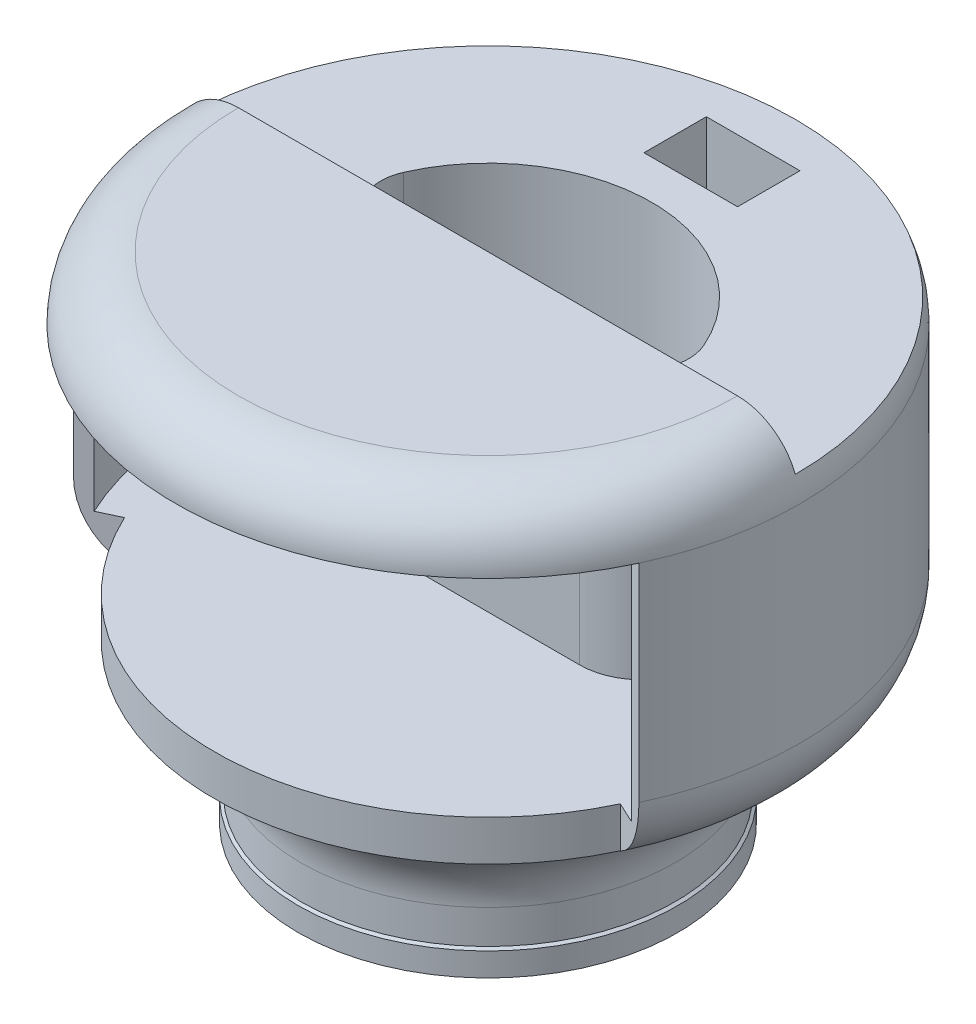
SolidWorks part; units mm, degrees
ref_plane "Front Plane" through (0, 0, 0) normal (0, 0, 1) x (1, 0, 0)
ref_plane "Top Plane" through (0, 0, 0) normal (0, 1, 0) x (1, 0, 0)
ref_plane "Right Plane" through (0, 0, 0) normal (1, 0, 0) x (0, 0, -1)
sketch "Sketch1" plane through (0, 0, 0) normal (0, 0, 1) x (1, 0, 0)
  line L0 (0, 0) -> (0, 90.2242) construction
  line L28 (0, 63.4279) -> (32, 63.4279)
  line L29 (40, 55.4279) -> (40, 28.8468)
  line L30 (22.5, 0) -> (24.35, 0)
  line L31 (24.35, 0) -> (24.35, 3)
  line L32 (24.35, 3) -> (24, 3.25)
  line L33 (24, 3.25) -> (24, 7.5811)
  line L34 (28.5399, 15.9588) -> (35.4601, 20.4691)
  line L35 (0, 13) -> (22, 13)
  line L36 (22.5, 12.5) -> (22.5, 0)
  line L37 (0, 13) -> (0, 63.4279)
  arc A0 (22, 13) -> (22.5, 12.5) centre (22, 12.5) cw
  arc A1 (24, 7.5811) -> (28.5399, 15.9588) centre (34, 7.5811) cw
  arc A2 (35.4601, 20.4691) -> (40, 28.8468) centre (30, 28.8468) ccw
  arc A3 (32, 63.4279) -> (40, 55.4279) centre (32, 55.4279) cw
  point P11 (22.9, 63.4279)
  point P18 (22.5, 13)
  point P21 (24, 13)
  point P24 (40, 23.4279)
  point P27 (40, 63.4279)
  point P28 (28.5604, 23.4279)
  point P31 (22.5, 17)
  dimension "D8" = 9.75
  dimension "D9" = 0.5
  dimension "D4" = 1.85
  dimension "D1" = 22.5
  dimension "D10" = 10
  dimension "D11" = 10
  dimension "D12" = 8
  dimension "D2" = 40
  dimension "D3" = 40
  dimension "D5" = 1.5
  dimension "D6" = 3
  dimension "D7" = 13
revolve "Revolve1" add sketch "Sketch1" angle 360 about L0
ref_plane "Plane1" through (0, 13, 0) normal (0, -1, 0) x (-1, 0, 0)
sketch "Sketch18" plane through (0, 0, 0) normal (0, 0, 1) x (1, 0, 0)
  line L0 (0, 0) -> (0, 101.5813) construction
  line L1 (-24.35, 0) -> (24.35, 0) construction
sketch "Sketch3" plane through (0, 0, 0) normal (0, 0, 1) x (1, 0, 0)
  point P0 (1.2404, 19.1989)
ref_point "Point1"
ref_plane "Plane2" through (0, 0, 22.9) normal (0, 0, 1) x (1, 0, 0)
ref_plane "Plane3" through (0, 0, 40) normal (0, 0, 1) x (1, 0, 0)
ref_plane "Plane4" through (0, 55.4279, 0) normal (0, 1, 0) x (1, 0, 0)
sketch "Sketch9" plane through (0, 55.4279, 0) normal (0, 1, 0) x (1, 0, 0)
  circle A7 centre (0, 0) radius 38
  circle A8 centre (0, 0) radius 40 construction
  circle A9 centre (0, 0) radius 23
  dimension "D1" = 2
  dimension "D2" = 46
ref_plane "Plane5" through (0, 13, 0) normal (0, -1, 0) x (-1, 0, 0)
sketch "Sketch11" plane through (0, 13, 0) normal (0, -1, 0) x (-1, 0, 0)
  line L0 (-21, 0) -> (21, 0)
  arc A1 (-21, 0) -> (21, 0) centre (0, 0) cw
  dimension "D1" = 42
extrude "Cut-Extrude3" cut sketch "Sketch11" against normal blind 60
ref_plane "Plane6" through (0, 0, -40) normal (0, 0, -1) x (-1, 0, 0)
extrude "Cut-Extrude5" cut sketch "Sketch9" against normal blind 30 and the other way blind 2
sketch "Sketch19" plane through (0, 0, 0) normal (1, 0, 0) x (0, 0, -1)
  line L0 (-47.0647, 55.4279) -> (-35.0647, 55.4279)
  line L1 (31.2976, 55.4279) -> (-31.2976, 55.4279) construction
  line L2 (-35.0647, 55.4279) -> (-35.0647, 18.9279)
  line L3 (-35.0647, 18.9279) -> (-47.0647, 18.9279)
  line L4 (-47.0647, 18.9279) -> (-47.0647, 55.4279)
  dimension "D1" = 12
  dimension "D2" = 36.5
revolve "Cut-Revolve2" cut sketch "Sketch19" angle 65 about L0 other way angle 65
ref_plane "Plane7" through (0, 0, 22.5) normal (0, 0, -1) x (-1, 0, 0)
sketch "Sketch21" plane through (0, 0, 22.5) normal (0, 0, -1) x (-1, 0, 0)
  line L0 (0, 0) -> (0, 101.5813) construction
  line L1 (-1.625, 4) -> (1.625, 4)
  line L2 (-1.625, 4) -> (-1.625, 0)
  line L3 (-1.625, 0) -> (1.625, 0)
  line L4 (1.625, 4) -> (1.625, 0)
  line L5 (-1.625, 4) -> (1.625, 0) construction
  line L6 (-1.625, 0) -> (1.625, 4) construction
  line L7 (-22.5, 0) -> (22.5, 0) construction
  point P0 (0, 2)
  dimension "D1" = 4
  dimension "D2" = 3.25
extrude "Boss-Extrude3" add sketch "Sketch21" along normal blind 1.35
pattern_circular "CirPattern1" count 5 over 360 about axis through (0, 0, 0) along (0, -1, 0) of "Boss-Extrude3"
ref_plane "Plane8" through (0, 20.4691, 0) normal (0, 1, 0) x (1, 0, 0)
sketch "Sketch22" plane through (0, 63.4279, 0) normal (0, 1, 0) x (1, 0, 0)
  line L0 (-40, 0) -> (40, 0)
  arc A0 (-40, 0) -> (40, 0) centre (0, 0) cw
  arc A1 (36.2523, -16.9047) -> (-36.2523, -16.9047) centre (0, 0) ccw construction
extrude "Cut-Extrude9" cut sketch "Sketch22" against normal blind 5
sketch "Sketch23" plane through (0, 0, -40) normal (0, 0, -1) x (-1, 0, 0)
  line L0 (0, 0) -> (0, 101.5813) construction
  line L1 (31.2976, 55.4279) -> (-31.2976, 55.4279) construction
  circle A0 centre (0, 42.1379) radius 10.5
  dimension "D1" = 21
  dimension "D2" = 13.29
extrude "Cut-Extrude10" cut sketch "Sketch23" against normal blind 10
sketch "Sketch24" plane through (0, 58.4279, 0) normal (0, 1, 0) x (1, 0, 0)
  line L1 (-8.5, 36) -> (8.5, 36)
  line L2 (-8.5, 36) -> (-8.5, 24)
  line L3 (-8.5, 24) -> (8.5, 24)
  line L4 (8.5, 36) -> (8.5, 24)
  line L5 (-8.5, 36) -> (8.5, 24) construction
  line L6 (-8.5, 24) -> (8.5, 36) construction
  arc A0 (39.4162, 0) -> (-39.4162, 0) centre (0, 0) ccw construction
  point P0 (0, 30)
  dimension "D1" = 30
  dimension "D2" = 12
  dimension "D3" = 17
extrude "Boss-Extrude4" add sketch "Sketch24" against normal blind 8
sketch "Sketch26" plane through (0, 58.4279, 0) normal (0, 1, 0) x (1, 0, 0)
  line L1 (-6, 34) -> (6, 34)
  line L2 (-6, 34) -> (-6, 26)
  line L3 (-6, 26) -> (6, 26)
  line L4 (6, 34) -> (6, 26)
  line L5 (-6, 34) -> (6, 26) construction
  line L6 (-6, 26) -> (6, 34) construction
  arc A0 (39.4162, 0) -> (-39.4162, 0) centre (0, 0) ccw construction
  point P0 (0, 30)
  dimension "D1" = 30
  dimension "D2" = 8
  dimension "D3" = 12
extrude "Cut-Extrude11" cut sketch "Sketch26" against normal blind 10
sketch "Sketch27" plane through (8.5, 0, 0) normal (1, 0, 0) x (0, 0, -1)
  line L0 (36, 50.4279) -> (36, 57.4279) construction
  line L1 (27.5, 56.4279) -> (31.5, 56.4279)
  line L2 (27.5, 56.4279) -> (27.5, 51.4279)
  line L3 (27.5, 51.4279) -> (31.5, 51.4279)
  line L4 (31.5, 56.4279) -> (31.5, 51.4279)
  line L5 (27.5, 56.4279) -> (31.5, 51.4279) construction
  line L6 (27.5, 51.4279) -> (31.5, 56.4279) construction
  line L7 (24, 50.4279) -> (24, 57.4279) construction
  line L8 (24, 50.4279) -> (36, 50.4279) construction
  point P0 (29.5, 53.9279)
  dimension "D1" = 12
  dimension "D2" = 3.5
  dimension "D3" = 5
  dimension "D4" = 4
  dimension "D5" = 5.5
extrude "Cut-Extrude12" cut sketch "Sketch27" against normal blind 5
ref_plane "Plane9" through (-39.4162, 58.4279, 0) normal (0.375, 0.927, 0) x (0.927, -0.375, 0)
ref_plane "Plane10" through (0, 58.4279, 0) normal (0, 1, 0) x (1, 0, 0)
sketch "Sketch28" plane through (0, 55.4279, 0) normal (0, 1, 0) x (1, 0, 0)
  line L0 (-22.9129, -2) -> (22.9129, -2)
  arc A0 (-22.9129, -2) -> (22.9129, -2) centre (0, 0) ccw
  dimension "D1" = 46
  dimension "D2" = 2
extrude "Cut-Extrude14" cut sketch "Sketch28" against normal blind 30 and the other way blind 2
sketch "Sketch29" plane through (0, 0, 0) normal (0, 0, -1) x (-1, 0, 0)
  line L0 (0, 0) -> (0, 101.5813) construction
  line L1 (32, 63.4279) -> (-32, 63.4279) construction
  circle A0 centre (-30.4162, 60.9279) radius 1
  circle A1 centre (30.4162, 60.9279) radius 1
  circle A2 centre (0, 60.9279) radius 1
  dimension "D1" = 2
  dimension "D2" = 2
  dimension "D3" = 2
  dimension "D4" = 2.5
  dimension "D5" = 2.5
  dimension "D6" = 2.5
  dimension "D7" = 9
  dimension "D8" = 9
extrude "Cut-Extrude15" cut sketch "Sketch29" against normal blind 15
fillet "Fillet1" radius 6 2 edges at (-21, 35.7139, 0) (21, 35.7139, 0)
fillet "Fillet2" radius 8 2 edges at (22.9129, 41.4279, 2) (-22.9129, 41.4279, 2)
